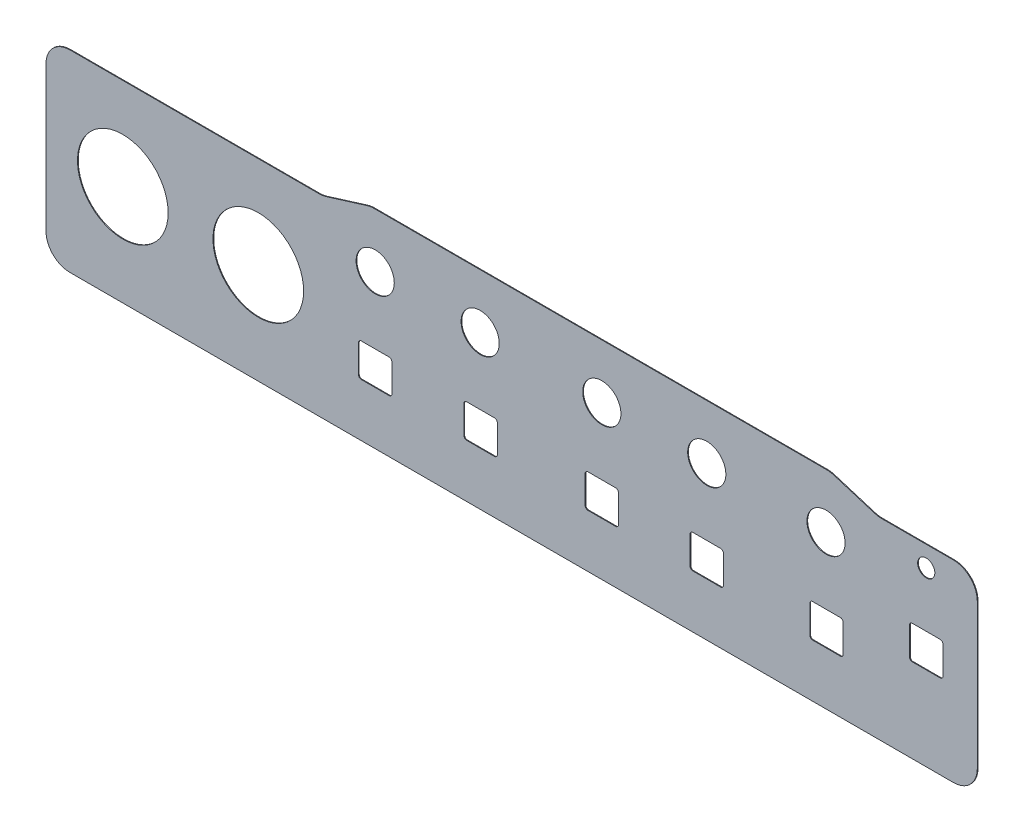
SolidWorks part; units mm, degrees
ref_plane "Спереди" through (0, 0, 0) normal (0, 0, 1) x (1, 0, 0)
ref_plane "Сверху" through (0, 0, 0) normal (0, 1, 0) x (1, 0, 0)
ref_plane "Справа" through (0, 0, 0) normal (1, 0, 0) x (0, 0, -1)
other "Configuration Table"
sketch "Printed_film_profile" plane through (0, 0, 0) normal (0, 0, 1) x (1, 0, 0)
  line L0 (2.4, -6.6) -> (187.6, -6.6)
  line L1 (192.6, -1.6) -> (192.6, 28.8)
  line L2 (187.6, 33.8) -> (172.5572, 33.8)
  line L3 (171.0767, 34.0242) -> (162.5233, 36.6758)
  line L4 (161.0428, 36.9) -> (66.1572, 36.9)
  line L5 (64.6767, 36.6758) -> (56.1233, 34.0242)
  line L6 (54.6428, 33.8) -> (2.4, 33.8)
  line L7 (-2.6, 28.8) -> (-2.6, -1.6)
  arc A0 (-2.6, -1.6) -> (2.4, -6.6) centre (2.4, -1.6) ccw
  arc A1 (187.6, -6.6) -> (192.6, -1.6) centre (187.6, -1.6) ccw
  arc A2 (192.6, 28.8) -> (187.6, 33.8) centre (187.6, 28.8) ccw
  arc A3 (172.5572, 33.8) -> (171.0767, 34.0242) centre (172.5572, 38.8) cw
  arc A4 (162.5233, 36.6758) -> (161.0428, 36.9) centre (161.0428, 31.9) ccw
  arc A5 (66.1572, 36.9) -> (64.6767, 36.6758) centre (66.1572, 31.9) ccw
  arc A6 (56.1233, 34.0242) -> (54.6428, 33.8) centre (54.6428, 38.8) cw
  arc A7 (2.4, 33.8) -> (-2.6, 28.8) centre (2.4, 28.8) ccw
extrude "Printed_film" add sketch "Printed_film_profile" along normal blind 0.15 from offset 15
sketch "Opening_BNC_Channel_0_profile" plane through (0, 0, 0) normal (0, 0, 1) x (1, 0, 0)
  circle A0 centre (13.5, 14.5) radius 9.5
extrude "Opening_BNC_Channel_0" cut sketch "Opening_BNC_Channel_0_profile" against normal blind 0.35 from offset 15.25
sketch "Opening_BNC_Channel_1_profile" plane through (0, 0, 0) normal (0, 0, 1) x (1, 0, 0)
  circle A0 centre (41.9, 14.5) radius 9.5
extrude "Opening_BNC_Channel_1" cut sketch "Opening_BNC_Channel_1_profile" against normal blind 0.35 from offset 15.25
sketch "Opening_LED_RUN_profile" plane through (0, 0, 0) normal (0, 0, 1) x (1, 0, 0)
  circle A0 centre (181.9, 29.5) radius 1.8
extrude "Opening_LED_RUN" cut sketch "Opening_LED_RUN_profile" against normal blind 0.35 from offset 15.25
sketch "Opening_FUNC_profile" plane through (0, 0, 0) normal (0, 0, 1) x (1, 0, 0)
  circle A0 centre (160.9, 25.5) radius 4
extrude "Opening_FUNC" cut sketch "Opening_FUNC_profile" against normal blind 0.35 from offset 15.25
sketch "Opening_TRG_MODE_profile" plane through (0, 0, 0) normal (0, 0, 1) x (1, 0, 0)
  line L0 (133, 4.5) -> (138.8, 4.5)
  line L1 (139.4, 5.1) -> (139.4, 10.9)
  line L2 (138.8, 11.5) -> (133, 11.5)
  line L3 (132.4, 10.9) -> (132.4, 5.1)
  arc A0 (138.8, 4.5) -> (139.4, 5.1) centre (138.8, 5.1) ccw
  arc A1 (139.4, 10.9) -> (138.8, 11.5) centre (138.8, 10.9) ccw
  arc A2 (133, 11.5) -> (132.4, 10.9) centre (133, 10.9) ccw
  arc A3 (132.4, 5.1) -> (133, 4.5) centre (133, 5.1) ccw
extrude "Opening_TRG_MODE" cut sketch "Opening_TRG_MODE_profile" against normal blind 0.35 from offset 15.25
sketch "Opening_CURSOR_profile" plane through (0, 0, 0) normal (0, 0, 1) x (1, 0, 0)
  line L0 (111, 4.5) -> (116.8, 4.5)
  line L1 (117.4, 5.1) -> (117.4, 10.9)
  line L2 (116.8, 11.5) -> (111, 11.5)
  line L3 (110.4, 10.9) -> (110.4, 5.1)
  arc A0 (116.8, 4.5) -> (117.4, 5.1) centre (116.8, 5.1) ccw
  arc A1 (117.4, 10.9) -> (116.8, 11.5) centre (116.8, 10.9) ccw
  arc A2 (111, 11.5) -> (110.4, 10.9) centre (111, 10.9) ccw
  arc A3 (110.4, 5.1) -> (111, 4.5) centre (111, 5.1) ccw
extrude "Opening_CURSOR" cut sketch "Opening_CURSOR_profile" against normal blind 0.35 from offset 15.25
sketch "Opening_EN_CH1_profile" plane through (0, 0, 0) normal (0, 0, 1) x (1, 0, 0)
  line L0 (85.6, 4.5) -> (91.4, 4.5)
  line L1 (92, 5.1) -> (92, 10.9)
  line L2 (91.4, 11.5) -> (85.6, 11.5)
  line L3 (85, 10.9) -> (85, 5.1)
  arc A0 (91.4, 4.5) -> (92, 5.1) centre (91.4, 5.1) ccw
  arc A1 (92, 10.9) -> (91.4, 11.5) centre (91.4, 10.9) ccw
  arc A2 (85.6, 11.5) -> (85, 10.9) centre (85.6, 10.9) ccw
  arc A3 (85, 5.1) -> (85.6, 4.5) centre (85.6, 5.1) ccw
extrude "Opening_EN_CH1" cut sketch "Opening_EN_CH1_profile" against normal blind 0.35 from offset 15.25
sketch "Opening_TRG_profile" plane through (0, 0, 0) normal (0, 0, 1) x (1, 0, 0)
  circle A0 centre (135.9, 25.5) radius 4
extrude "Opening_TRG" cut sketch "Opening_TRG_profile" against normal blind 0.35 from offset 15.25
sketch "Opening_TIME_profile" plane through (0, 0, 0) normal (0, 0, 1) x (1, 0, 0)
  circle A0 centre (113.9, 25.5) radius 4
extrude "Opening_TIME" cut sketch "Opening_TIME_profile" against normal blind 0.35 from offset 15.25
sketch "Opening_SET_CH1_profile" plane through (0, 0, 0) normal (0, 0, 1) x (1, 0, 0)
  circle A0 centre (88.4, 25.5) radius 4
extrude "Opening_SET_CH1" cut sketch "Opening_SET_CH1_profile" against normal blind 0.35 from offset 15.25
sketch "Opening_SET_CH0_profile" plane through (0, 0, 0) normal (0, 0, 1) x (1, 0, 0)
  circle A0 centre (66.4, 25.5) radius 4
extrude "Opening_SET_CH0" cut sketch "Opening_SET_CH0_profile" against normal blind 0.35 from offset 15.25
sketch "Opening_RUN_STOP_profile" plane through (0, 0, 0) normal (0, 0, 1) x (1, 0, 0)
  line L0 (179, 11) -> (184.8, 11)
  line L1 (185.4, 11.6) -> (185.4, 17.4)
  line L2 (184.8, 18) -> (179, 18)
  line L3 (178.4, 17.4) -> (178.4, 11.6)
  arc A0 (184.8, 11) -> (185.4, 11.6) centre (184.8, 11.6) ccw
  arc A1 (185.4, 17.4) -> (184.8, 18) centre (184.8, 17.4) ccw
  arc A2 (179, 18) -> (178.4, 17.4) centre (179, 17.4) ccw
  arc A3 (178.4, 11.6) -> (179, 11) centre (179, 11.6) ccw
extrude "Opening_RUN_STOP" cut sketch "Opening_RUN_STOP_profile" against normal blind 0.35 from offset 15.25
sketch "Opening_MENU_BACK_profile" plane through (0, 0, 0) normal (0, 0, 1) x (1, 0, 0)
  line L0 (158.1, 4.5) -> (163.9, 4.5)
  line L1 (164.5, 5.1) -> (164.5, 10.9)
  line L2 (163.9, 11.5) -> (158.1, 11.5)
  line L3 (157.5, 10.9) -> (157.5, 5.1)
  arc A0 (163.9, 4.5) -> (164.5, 5.1) centre (163.9, 5.1) ccw
  arc A1 (164.5, 10.9) -> (163.9, 11.5) centre (163.9, 10.9) ccw
  arc A2 (158.1, 11.5) -> (157.5, 10.9) centre (158.1, 10.9) ccw
  arc A3 (157.5, 5.1) -> (158.1, 4.5) centre (158.1, 5.1) ccw
extrude "Opening_MENU_BACK" cut sketch "Opening_MENU_BACK_profile" against normal blind 0.35 from offset 15.25
sketch "Opening_EN_CH0_profile" plane through (0, 0, 0) normal (0, 0, 1) x (1, 0, 0)
  line L0 (63.5, 4.5) -> (69.3, 4.5)
  line L1 (69.9, 5.1) -> (69.9, 10.9)
  line L2 (69.3, 11.5) -> (63.5, 11.5)
  line L3 (62.9, 10.9) -> (62.9, 5.1)
  arc A0 (69.3, 4.5) -> (69.9, 5.1) centre (69.3, 5.1) ccw
  arc A1 (69.9, 10.9) -> (69.3, 11.5) centre (69.3, 10.9) ccw
  arc A2 (63.5, 11.5) -> (62.9, 10.9) centre (63.5, 10.9) ccw
  arc A3 (62.9, 5.1) -> (63.5, 4.5) centre (63.5, 5.1) ccw
extrude "Opening_EN_CH0" cut sketch "Opening_EN_CH0_profile" against normal blind 0.35 from offset 15.25
